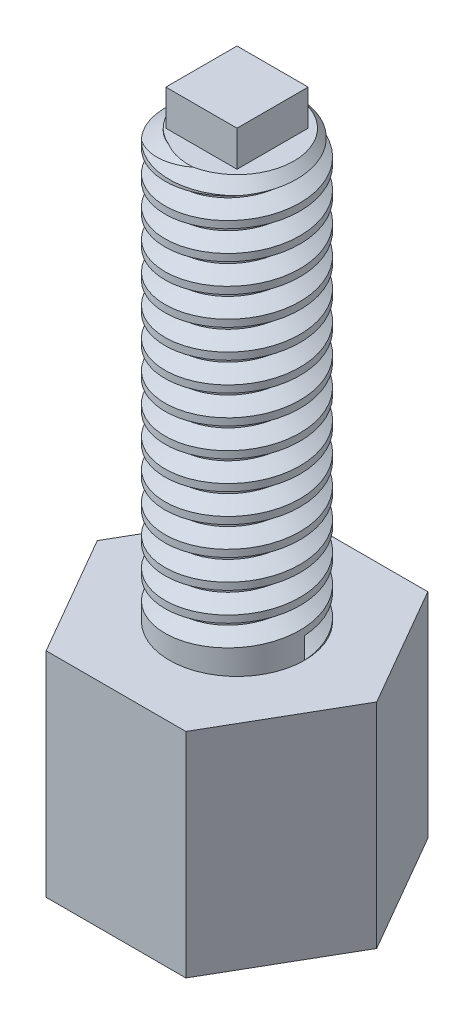
SolidWorks part; units mm, degrees
ref_plane "Front Plane" through (0, 0, 0) normal (0, 0, 1) x (1, 0, 0)
ref_plane "Top Plane" through (0, 0, 0) normal (0, 1, 0) x (1, 0, 0)
ref_plane "Right Plane" through (0, 0, 0) normal (1, 0, 0) x (0, 0, -1)
sketch "Sketch1" plane through (0, 0, 0) normal (0, 1, 0) x (1, 0, 0)
  line L1 (19.6299, 0) -> (9.815, 17)
  line L2 (9.815, 17) -> (-9.815, 17)
  line L3 (-9.815, 17) -> (-19.6299, 0)
  line L4 (-19.6299, 0) -> (-9.815, -17)
  line L5 (-9.815, -17) -> (9.815, -17)
  line L6 (9.815, -17) -> (19.6299, 0)
  circle A1 centre (0, 0) radius 17 construction
extrude "Boss-Extrude1" add sketch "Sketch1" along normal mid plane 30
sketch "Sketch2" plane through (0, 15, 0) normal (0, 1, 0) x (1, 0, 0)
  circle A0 centre (0, 0) radius 9.5
extrude "Boss-Extrude2" add sketch "Sketch2" along normal blind 60 contours A0
chamfer "Chamfer1" distance 1.5 angle 45 1 edges at (0, 75, 9.5)
thread "Thread3" pitch 4 method cut profile "Thread Profile3" start angle 0, offset 0, length 0, pitch 4, diameter 19
ref_plane "Plane3" through (9.5, 15, 0) normal (0, 0, -1) x (-1, 0, 0)
sketch "Thread Profile3" plane through (9.5, 15, 0) normal (0, 0, -1) x (-1, 0, 0)
  line L0 (0, 0) -> (0, 4) construction
  line L1 (0, 0) -> (2.1651, 1.25)
  line L2 (2.1651, 1.25) -> (2.1651, 1.75)
  line L3 (2.1651, 1.75) -> (0, 3)
  line L4 (2.1651, 1.5) -> (0, 1.5) construction
  line L11 (0, 0) -> (0, 3)
  point P2 (0, 0)
  dimension "Pitch" = 4
  dimension "Profile_Angle" = 60
  dimension "Profile_Land" = 0.5
  dimension "Profile_Height" = 2.1651
sketch "Sketch19" plane through (0, 75, 0) normal (0, 1, 0) x (1, 0, 0)
  line L1 (5, 5) -> (-5, 5)
  line L2 (5, 5) -> (5, -5)
  line L3 (5, -5) -> (-5, -5)
  line L4 (-5, 5) -> (-5, -5)
  line L5 (5, 5) -> (-5, -5) construction
  line L6 (5, -5) -> (-5, 5) construction
  point P0 (0, 0)
extrude "Boss-Extrude4" add sketch "Sketch19" along normal blind 5 contours L4 L3 L2 L1
